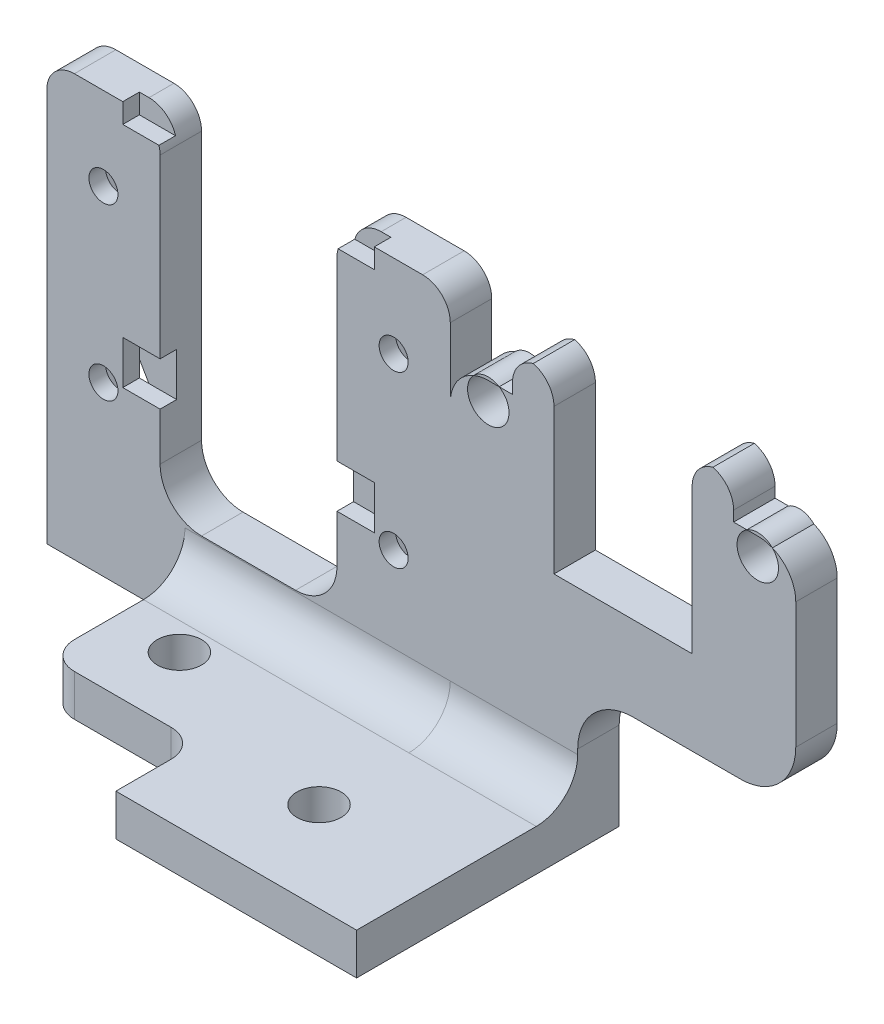
SolidWorks part; units mm, degrees
ref_plane "Plano frontal" through (0, 0, 0) normal (0, 0, 1) x (1, 0, 0)
ref_plane "Plano superior" through (0, 0, 0) normal (0, 1, 0) x (1, 0, 0)
ref_plane "Plano direito" through (0, 0, 0) normal (1, 0, 0) x (0, 0, -1)
sketch "Esboço2" plane through (0, 0, -1) normal (0, 0, -1) x (-1, 0, 0)
  line L1 (14.6, 8.1) -> (6.4, 8.1)
  line L2 (14.6, 8.1) -> (14.6, -22.3604)
  line L3 (14.6, -22.3604) -> (6.4, -22.3604)
  line L4 (6.4, 8.1) -> (6.4, -22.3604)
  line L5 (6.4, 8.1) -> (-21.6025, 8.1) construction
  line L6 (-12.6, -12) -> (-12.6, 12) construction
  line L7 (-14.6, 8.1) -> (-6.4, 8.1)
  line L8 (-14.6, 8.1) -> (-14.6, -22.3604)
  line L9 (-14.6, -22.3604) -> (-6.4, -22.3604)
  line L10 (-6.4, 8.1) -> (-6.4, -22.3604)
  line L11 (12.6, -12) -> (12.6, 12) construction
  line L12 (-4.4, -2.7) -> (-4.4, 6.1) construction
  circle A0 centre (-10.5, 2.1) radius 1.05 construction
  dimension "D3" = 6
  dimension "D1" = 2
  dimension "D2" = 2
  dimension "D4" = 2
extrude "Ressalto-extrusão1" add sketch "Esboço2" along normal blind 3
sketch "Esboço3" plane through (-6.4, 0, 0) normal (1, 0, 0) x (0, 0, -1)
  line L0 (4, 8.1) -> (4, -22.3604) construction
  line L1 (1, -22.3604) -> (4, -22.3604)
  line L2 (1, -22.3604) -> (1, -16.2722)
  line L3 (1, -16.2722) -> (4, -16.2722)
  line L4 (4, -22.3604) -> (4, -16.2722)
extrude "Ressalto-extrusão2" add sketch "Esboço3" along normal up to next
sketch "Esboço4" plane through (0, 0, -1) normal (0, 0, 1) x (1, 0, 0)
  line L0 (14.6, -22.3604) -> (-14.6, -22.3604) construction
  line L1 (-6.4, -22.3604) -> (6.4, -22.3604)
  line L2 (-6.4, -22.3604) -> (-6.4, -19.3604)
  line L3 (-6.4, -19.3604) -> (6.4, -19.3604)
  line L4 (6.4, -22.3604) -> (6.4, -19.3604)
  line L5 (6.4, -16.2722) -> (6.4, 8.1) construction
  line L6 (-6.4, 8.1) -> (-6.4, -16.2722) construction
  dimension "D1" = 3
extrude "Ressalto-extrusão3" add sketch "Esboço4" along normal blind 10
sketch "Esboço5" plane through (0, 0, -1) normal (0, 0, 1) x (1, 0, 0)
  line L0 (14.6, 8.1) -> (14.6, -22.3604) construction
  line L1 (-14.6, -22.3604) -> (-6.4, -22.3604)
  line L2 (-14.6, -22.3604) -> (-14.6, -19.3604)
  line L3 (-14.6, -19.3604) -> (-6.4, -19.3604)
  line L4 (-6.4, -22.3604) -> (-6.4, -19.3604)
  line L5 (6.4, -22.3604) -> (14.6, -22.3604)
  line L6 (6.4, -22.3604) -> (6.4, -19.3604)
  line L7 (6.4, -19.3604) -> (14.6, -19.3604)
  line L8 (14.6, -22.3604) -> (14.6, -19.3604)
  line L9 (-6.4, -19.3604) -> (-6.4, -22.3604) construction
  dimension "D1" = 3
extrude "Ressalto-extrusão4" add sketch "Esboço5" along normal blind 16
sketch "Esboço6" plane through (0, -19.3604, 0) normal (0, 1, 0) x (1, 0, 0)
  line L0 (6.4, -9) -> (-6.4, 1) construction
  line L1 (6.4, -15) -> (6.4, -9) construction
  line L2 (-14.6, -10.5) -> (-6.4, -10.5) construction
  line L3 (-14.6, -15) -> (-14.6, 1) construction
  line L4 (-6.4, -15) -> (-6.4, -9) construction
  line L5 (-6.4, -10.5) -> (6.4, -10.5) construction
  line L6 (6.4, -10.5) -> (14.6, -10.5) construction
  line L7 (14.6, -15) -> (14.6, 1) construction
  line L8 (14.6, -15) -> (6.4, -15) construction
  circle A0 centre (0, -4) radius 1.6
  circle A1 centre (10.5, -10.5) radius 1.6
  circle A2 centre (-10.5, -10.5) radius 1.6
  dimension "D1" = 3.2
  dimension "D2" = 4.5
sketch "Esboço8" plane through (0, 0, -1) normal (0, 0, 1) x (1, 0, 0)
  circle A0 centre (-10.5, 2.1) radius 1.05
  circle A1 centre (10.5, 2.1) radius 1.05
  circle A2 centre (10.5, -10.2) radius 1.05
  circle A3 centre (-10.5, -10.2) radius 1.05
  dimension "D1" = 2.1
extrude "Corte-extrusão3" cut sketch "Esboço8" against normal through all
fillet "Filete1" radius 3 2 edges at (6.4, -16.2722, -2.5) (-6.4, -16.2722, -2.5)
sketch "Esboço9" plane through (6.4, 0, 0) normal (-1, 0, 0) x (0, 0, 1)
  line L0 (-1, -13.2722) -> (-1, 8.1) construction
  line L1 (-1, -6.6712) -> (-2.2, -6.6712)
  line L2 (-1, -6.6712) -> (-1, -9.82)
  line L3 (-1, -9.82) -> (-2.2, -9.82)
  line L4 (-2.2, -6.6712) -> (-2.2, -9.82)
extrude "Corte-extrusão4" cut sketch "Esboço9" against normal blind 2.7
fillet "Filete2" radius 3 1 edges at (0, -19.3604, -1)
sketch "Esboço10" plane through (0, 0, -4) normal (0, 0, -1) x (-1, 0, 0)
  line L0 (0, -16.2722) -> (0, 4.5459) construction
  line L1 (12.8094, 2.1) -> (11.6547, 4.1)
  line L2 (11.6547, 4.1) -> (9.3453, 4.1)
  line L3 (9.3453, 4.1) -> (8.1906, 2.1)
  line L4 (8.1906, 2.1) -> (9.3453, 0.1)
  line L5 (9.3453, 0.1) -> (11.6547, 0.1)
  line L6 (11.6547, 0.1) -> (12.8094, 2.1)
  line L7 (12.8094, -10.2) -> (11.6547, -8.2)
  line L8 (11.6547, -8.2) -> (9.3453, -8.2)
  line L9 (9.3453, -8.2) -> (8.1906, -10.2)
  line L10 (8.1906, -10.2) -> (9.3453, -12.2)
  line L11 (9.3453, -12.2) -> (11.6547, -12.2)
  line L12 (11.6547, -12.2) -> (12.8094, -10.2)
  line L13 (-3.4, -16.2722) -> (3.4, -16.2722) construction
  line L14 (-11.6547, -12.2) -> (-12.8094, -10.2)
  line L15 (-9.3453, -12.2) -> (-11.6547, -12.2)
  line L16 (-8.1906, -10.2) -> (-9.3453, -12.2)
  line L17 (-9.3453, -8.2) -> (-8.1906, -10.2)
  line L18 (-11.6547, -8.2) -> (-9.3453, -8.2)
  line L19 (-12.8094, -10.2) -> (-11.6547, -8.2)
  line L20 (-11.6547, 0.1) -> (-12.8094, 2.1)
  line L21 (-9.3453, 0.1) -> (-11.6547, 0.1)
  line L22 (-8.1906, 2.1) -> (-9.3453, 0.1)
  line L23 (-9.3453, 4.1) -> (-8.1906, 2.1)
  line L24 (-11.6547, 4.1) -> (-9.3453, 4.1)
  line L25 (-12.8094, 2.1) -> (-11.6547, 4.1)
  circle A0 centre (10.5, 2.1) radius 2 construction
  circle A1 centre (10.5, -10.2) radius 2 construction
  circle A2 centre (-10.5, -10.2) radius 2 construction
  circle A3 centre (-10.5, 2.1) radius 2 construction
  point P25 (10.5, 0.1)
  dimension "D1" = 4
extrude "Corte-extrusão5" cut sketch "Esboço10" against normal blind 1.8
sketch "Esboço11" plane through (0, -19.3604, 0) normal (0, 1, 0) x (1, 0, 0)
  line L0 (0, 0) -> (0, -34) construction
  line L1 (8.25, -11) -> (-8.25, -11)
  line L2 (8.25, -11) -> (8.25, -17)
  line L3 (8.25, -17) -> (-8.25, -17)
  line L4 (-8.25, -11) -> (-8.25, -17)
  line L5 (6.4, -9) -> (-6.4, -9) construction
  point P7 (0, -17)
  dimension "D1" = 16.5
  dimension "D2" = 6
  dimension "D3" = 2
sketch "Esboço13" plane through (0, 0, -1) normal (0, 0, 1) x (1, 0, 0)
  line L0 (12.6426, 0) -> (0, 0) construction
  line L1 (12.6426, 12) -> (12.6426, -12) construction
  line L2 (9.1, -6.6712) -> (6.4, -6.6712) construction
  line L3 (6.4, -6.6712) -> (6.4, -9.82) construction
  line L4 (9.1, -9.82) -> (6.4, -9.82) construction
  line L5 (9.1, -9.82) -> (9.1, -6.6712) construction
  line L6 (9.1, -6.6712) -> (6.4, -6.6712)
  line L7 (6.4, -6.6712) -> (6.4, -9.82)
  line L8 (9.1, -9.82) -> (6.4, -9.82)
  line L9 (9.1, -9.82) -> (9.1, -6.6712)
  line L10 (0, 0) -> (0, -9.82) construction
  line L11 (9.1, 9.82) -> (9.1, 6.6712)
  line L12 (9.1, 9.82) -> (6.4, 9.82)
  line L13 (6.4, 6.6712) -> (6.4, 9.82)
  line L14 (9.1, 6.6712) -> (6.4, 6.6712)
  line L15 (-9.1, 6.6712) -> (-6.4, 6.6712)
  line L16 (-6.4, 6.6712) -> (-6.4, 9.82)
  line L17 (-9.1, 9.82) -> (-6.4, 9.82)
  line L18 (-9.1, 9.82) -> (-9.1, 6.6712)
  line L19 (-9.1, -9.82) -> (-9.1, -6.6712)
  line L20 (-9.1, -9.82) -> (-6.4, -9.82)
  line L21 (-6.4, -6.6712) -> (-6.4, -9.82)
  line L22 (-9.1, -6.6712) -> (-6.4, -6.6712)
extrude "Corte-extrusão7" cut sketch "Esboço13" against normal up to surface (1.2 mm away) up to face at (7.882, -8.3215, -2.2)
sketch "Esboço14" plane through (14.6, 0, 0) normal (1, 0, 0) x (0, 0, -1)
  line L0 (-15, -19.3604) -> (4, -19.3604)
  line L1 (4, 8.1) -> (4, -22.3604) construction
  line L2 (4, -19.3604) -> (4, -22.3604)
  line L3 (4, -22.3604) -> (-15, -22.3604)
  line L4 (-15, -22.3604) -> (-15, -19.3604)
extrude "Ressalto-extrusão5" add sketch "Esboço14" along normal blind 25
sketch "Esboço15" plane through (0, -19.3604, 0) normal (0, 1, 0) x (1, 0, 0)
  line L0 (14.6, 1) -> (39.6, 1)
  line L1 (39.6, 4) -> (39.6, -15) construction
  line L2 (39.6, 1) -> (39.6, 4)
  line L3 (39.6, 4) -> (14.6, 4)
  line L4 (14.6, 4) -> (14.6, 1)
  dimension "D1" = 3
extrude "Ressalto-extrusão6" add sketch "Esboço15" along normal blind 25.96
sketch "Esboço16" plane through (0, 0, -4) normal (0, 0, -1) x (-1, 0, 0)
  line L0 (-14.6, 8.1) -> (-14.6, -16.6485) construction
  line L1 (-39.6, 1.0996) -> (-14.6, 1.0996) construction
  line L2 (-39.6, -22.3604) -> (-39.6, 6.5996) construction
  line L3 (-39.6, 6.5996) -> (-14.6, 6.5996) construction
  line L4 (-27.1, 6.5996) -> (-27.1, -12.0071) construction
  line L5 (-35.1, 6.5996) -> (-35.1, 3.8496) construction
  line L6 (-35.1, 3.8496) -> (-36.85, 3.8496)
  line L7 (-36.85, -1.6504) -> (-35.1, -1.6504)
  line L8 (-35.1, -1.6504) -> (-35.1, -7.4004)
  line L9 (-36.85, 3.8496) -> (-36.85, -4.4528) construction
  line L10 (-35.1, 6.5996) -> (-35.1, 3.8496)
  line L11 (-35.1, 6.5996) -> (-32.1, 6.5996)
  line L12 (-32.1, 6.5996) -> (-32.1, -5.9004)
  line L13 (-35.1, -7.4004) -> (-35.1, -10.4004)
  line L14 (-35.1, -10.4004) -> (-27.1, -10.4004)
  line L15 (-32.1, -5.9004) -> (-22.1, -5.9004)
  line L16 (-19.1, -7.4004) -> (-19.1, -10.4004)
  line L17 (-19.1, -1.6504) -> (-19.1, -7.4004)
  line L18 (-17.35, -1.6504) -> (-19.1, -1.6504)
  line L19 (-19.1, 3.8496) -> (-17.35, 3.8496)
  line L20 (-19.1, 6.5996) -> (-19.1, 3.8496)
  line L21 (-19.1, 6.5996) -> (-22.1, 6.5996)
  line L22 (-22.1, 6.5996) -> (-22.1, -5.9004)
  line L23 (-27.1, -10.4004) -> (-19.1, -10.4004)
  line L24 (-32.1, 6.5996) -> (-22.1, 6.5996)
  line L25 (-39.6, -12.0071) -> (-27.1, -12.0071)
  line L27 (-23.82, -19.3604) -> (-39.6, -19.3604)
  line L28 (-39.6, -22.3604) -> (14.6, -22.3604) construction
  line L29 (-14.6, 8.1) -> (-14.6, 1.0996)
  line L30 (-19.1, 6.5996) -> (-14.6, 8.1)
  line L31 (-39.6, -12.0071) -> (-39.6, -19.3604)
  line L32 (-23.82, -19.3604) -> (-23.82, -12.0071)
  line L33 (-23.82, -12.0071) -> (-27.1, -12.0071)
  arc A0 (-36.85, 3.8496) -> (-36.85, -1.6504) centre (-36.85, 1.0996) ccw
  circle A1 centre (-36.85, 2.5741) radius 1.5
  circle A2 centre (-17.35, 2.5741) radius 1.5
  arc A3 (-17.35, 3.8496) -> (-17.35, -1.6504) centre (-17.35, 1.0996) cw
  point P38 (-27.1, -5.9004)
  line M37 (-14.6, 6.5996) -> (-39.6, 6.5996)
  line M38 (-39.6, 6.5996) -> (-39.6, -22.3604)
  dimension "D6" = 1.75
  dimension "D1" = 5.5
  dimension "D2" = 12.5
  dimension "D3" = 2.75
  dimension "D4" = 1.75
  dimension "D5" = 8
  dimension "D7" = 5.75
  dimension "D8" = 3
  dimension "D9" = 3
  dimension "D10" = 3
  dimension "D11" = 15.78
extrude "Corte-extrusão8" cut sketch "Esboço16" against normal blind 26 contours L27 L25 M38 | A1 | A0 L6 L10 M37 M38 | L22 L12 L15 M37 | A2 | L19 A3 L29 L20 M37 region at (37.5517, 5.0166, -4) region at (36.8451, 2.5173, -4) region at (31.71, -15.6837, -4) region at (27.1, 0.3496, -4) region at (16.6483, 5.0166, -4) region at (17.3549, 2.5173, -4)
fillet "Filete4" radius 4 1 edges at (39.6, -12.0071, -2.5)
fillet "Filete5" radius 2 8 edges at (-14.6, 8.1, -2.5) (-6.4, 8.1, -3.1) (6.4, 8.1, -3.1) (14.6, 8.1, -2.5) (19.1, 6.5996, -2.5) (22.1, 6.5996, -2.5) (35.1, 6.5996, -2.5) (32.1, 6.5996, -2.5)
sketch "Esboço18" plane through (-14.6, 0, 0) normal (-1, 0, 0) x (0, 0, 1)
  line L0 (-1, -16.3604) -> (-1, -22.3604)
  line L1 (-4, -22.3604) -> (15, -22.3604) construction
  line L2 (-1, -22.3604) -> (15, -22.3604)
  line L3 (15, -22.3604) -> (15, -19.3604)
  line L4 (15, -19.3604) -> (-1, -16.3604)
extrude "Corte-extrusão10" cut sketch "Esboço18" against normal blind 10
sketch "Esboço19" plane through (39.6, 0, 0) normal (1, 0, 0) x (0, 0, -1)
  line L0 (-15, -17.3604) -> (-15, -22.3604)
  line L1 (-15, -22.3604) -> (4, -22.3604)
  line L2 (4, -22.3604) -> (4, -17.3604)
  line L3 (4, -17.3604) -> (-15, -17.3604)
  dimension "D1" = 5
extrude "Corte-extrusão13" cut sketch "Esboço19" against normal blind 15.78
fillet "Filete7" radius 4 1 edges at (23.82, -12.0071, -2.5)
fillet "Filete8" radius 3 1 edges at (19.21, -19.3604, -1)
sketch "Esboço20" plane through (0, -19.3604, 0) normal (0, 1, 0) x (1, 0, 0)
  line L0 (14.6, -2) -> (14.6, -15) construction
  line L1 (23.82, -15) -> (6.4, -15) construction
  circle A0 centre (14.6, -8.5) radius 1.6
  circle A1 centre (0, -4) radius 1.6
extrude "Corte-extrusão14" cut sketch "Esboço20" against normal blind 12
fillet "Filete9" radius 2 2 edges at (6.4, -20.8604, 9) (-4.6, -20.8604, 9)
